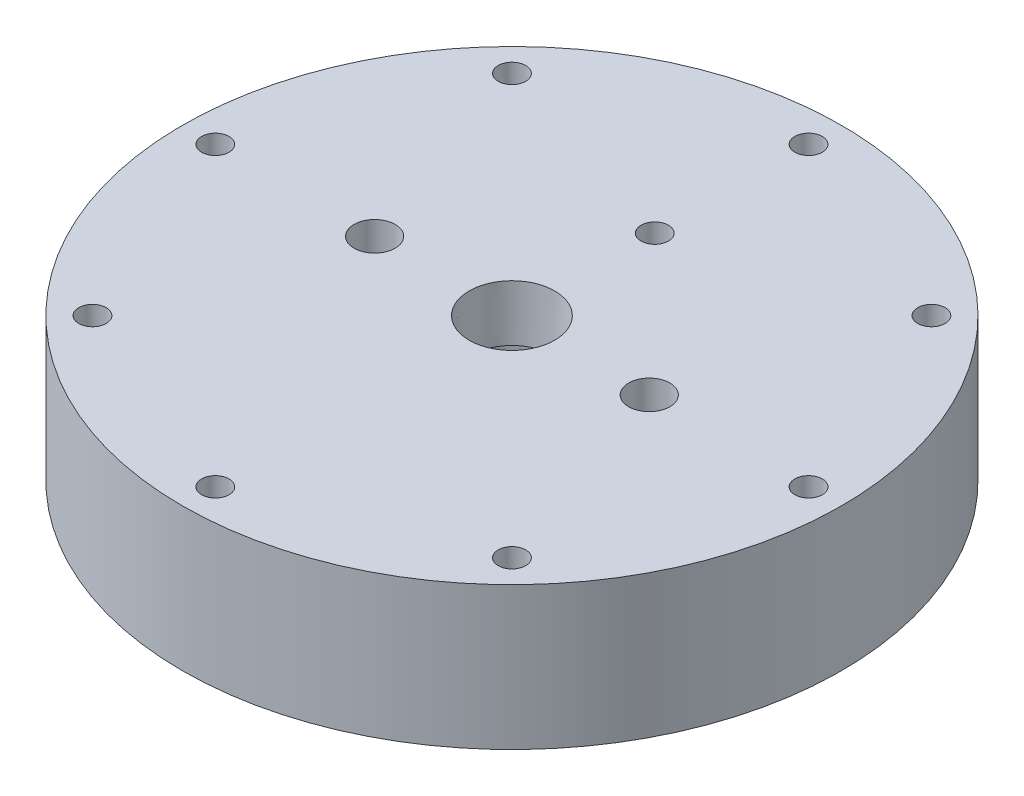
SolidWorks part; units mm, degrees
ref_plane "Front Plane" through (0, 0, 0) normal (0, 0, 1) x (1, 0, 0)
ref_plane "Top Plane" through (0, 0, 0) normal (0, 1, 0) x (1, 0, 0)
ref_plane "Right Plane" through (0, 0, 0) normal (1, 0, 0) x (0, 0, -1)
ref_axis "Axial" through (0, 53.34, 0) along (0, -1, 0)
ref_plane "Bottom Plane" through (0, -50.8, 0) normal (0, 1, 0) x (1, 0, 0)
sketch "Sketch1" plane through (0, 0, 0) normal (0, 1, 0) x (1, 0, 0)
  circle A0 centre (0, 0) radius 76.2
  dimension "D1" = 152.4
extrude "Billet" add sketch "Sketch1" against normal blind 50.8
sketch "Sketch3" plane through (0, -50.8, 0) normal (0, 1, 0) x (1, 0, 0)
  circle A0 centre (0, 0) radius 19.05
  dimension "D1" = 38.1
extrude "Lox Plate" cut sketch "Sketch3" along normal blind 13.97
sketch "Sketch5" plane through (0, -50.8, 0) normal (0, 1, 0) x (1, 0, 0)
  circle A0 centre (0, 0) radius 13.97
  dimension "D1" = 27.94
extrude "Lox Dome" cut sketch "Sketch5" along normal blind 20.32
sketch "Sketch7" plane through (0, 0, 0) normal (0, 1, 0) x (1, 0, 0)
  circle A1 centre (0, 0) radius 76.2
  dimension "D2" = 152.4
extrude "Top Mill" cut sketch "Sketch7" against normal blind 17.78
sketch "Sketch11" plane through (0, -50.8, 0) normal (0, 1, 0) x (1, 0, 0)
  line L0 (0, 82.3071) -> (0, -82.946) construction
  circle A0 centre (0, 68.58) radius 3.175
  dimension "D1" = 6.35
  dimension "D2" = 68.58
extrude "1/4\" Bolt Hole" cut sketch "Sketch11" along normal up to next
pattern_circular "Bolt Pattern" count 8 over 360 about axis through (0, 53.34, 0) along (0, -1, 0) of "1/4\" Bolt Hole"
sketch "Sketch12" plane through (0, -50.8, 0) normal (0, 1, 0) x (1, 0, 0)
  circle A0 centre (0, 0) radius 57.15
extrude "Kerosene Plate" cut sketch "Sketch12" along normal blind 10.16
sketch "Sketch13" plane through (0, 0, 0) normal (0, 1, 0) x (1, 0, 0)
  line L0 (-57.2849, 0) -> (80.0711, 0) construction
  line L1 (0, 48.6602) -> (0, -50.5768) construction
  circle A0 centre (-31.75, 0) radius 4.7625
  circle A1 centre (31.75, 0) radius 4.7625
  dimension "D1" = 9.525
  dimension "D2" = 31.75
extrude "Kerosene Inlet" cut sketch "Sketch13" against normal up to next
sketch "Sketch14" plane through (0, 0, 0) normal (0, 1, 0) x (1, 0, 0)
  line L0 (0, 82.1507) -> (0, -86.6258) construction
  circle A0 centre (0, 33.02) radius 3.175
  dimension "D1" = 6.35
  dimension "D2" = 33.02
extrude "Manifold hole" cut sketch "Sketch14" against normal up to next
sketch "Sketch15" plane through (0, -50.8, 0) normal (0, 1, 0) x (1, 0, 0)
  line L0 (0, 72.5611) -> (0, -49.1199) construction
  circle A0 centre (0, 33.02) radius 7.62
  circle A1 centre (0, 33.02) radius 10.16
  dimension "D1" = 15.24
  dimension "D2" = 20.32
extrude "Manifold seal" cut sketch "Sketch15" along normal blind 12.192
hole_wizard "1/2 NPT Tapped Hole3" positions "Sketch20" profile "Sketch21" size "1/2" standard "ANSI Inch" end condition through all
sketch "Sketch20" plane through (0, -17.78, 0) normal (0, 1, 0) x (1, 0, 0)
  point P0 (0, 0)
cosmetic thread "Hole Thread3" parameters "D1"=13.462, "D2"=21.3295
sketch "Sketch21" plane through (0, -17.78, 0) normal (1, 0, 0) x (0, 0, 1)
  line L0 (0, 0) -> (0, 33.02)
  line L1 (0, 33.02) -> (8.9281, 33.02)
  line L2 (-9.4797, 13.462) -> (-9.8828, 0) construction
  line L3 (8.9281, 33.02) -> (8.9281, 13.462)
  line L4 (8.9281, 13.462) -> (9.4797, 13.462)
  line L5 (9.4797, 13.462) -> (9.8828, 0)
  line L7 (9.8828, 0) -> (0, 0)
  line L8 (0, -6.35) -> (0, 107.95) construction
  line L11 (-8.9281, 13.462) -> (-9.4797, 13.462) construction
  dimension "Thru Tap Drill Dia." = 17.8562
  dimension "Thru Tap Drill Depth" = 33.02
  dimension "Thread Dia." = 19.7656
  dimension "Thread Angle" = 3.43
  dimension "Thread Depth" = 13.462
